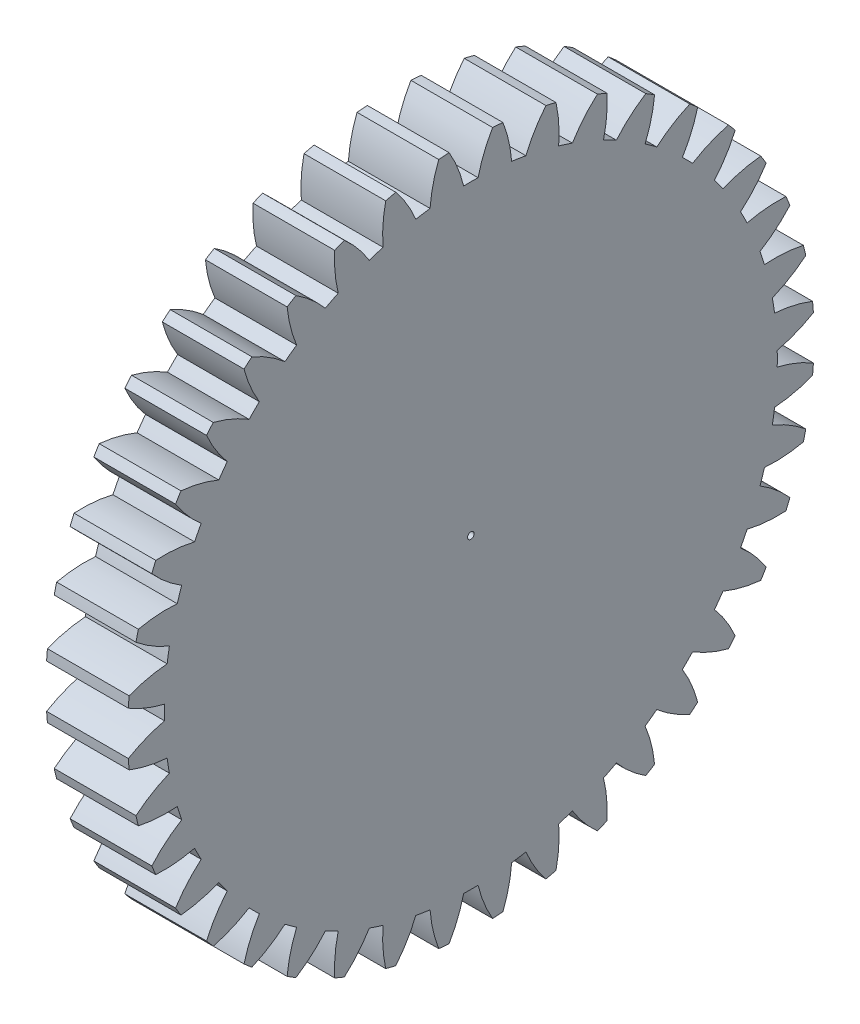
SolidWorks part; units mm, degrees
ref_plane "Plane1" through (0, 0, 0) normal (0, 0, 1) x (1, 0, 0)
ref_plane "Plane2" through (0, 0, 0) normal (0, 1, 0) x (1, 0, 0)
ref_plane "Plane3" through (0, 0, 0) normal (1, 0, 0) x (0, 0, -1)
sketch "HoldingSke" plane through (0, 0, 0) normal (0, 1, 0) x (1, 0, 0)
  line L0 (0, 0) -> (0.383, -0.3214)
  line L1 (-15, 0) -> (100, 0) construction
  line L2 (0, 0) -> (-2.1039, 2.3779)
  line L3 (0, 0) -> (-11.863, 4.5341)
  line L4 (0, 0) -> (6.6156, 5.5511)
  line L5 (0, 0) -> (-46.8476, -17.4728)
  line L6 (0, 0) -> (-8.2896, -5.593)
  line L7 (-2.1039, 2.3779) -> (8.6586, 51.2059)
  line L8 (-76.2, 54.61) -> (-76.1, 54.61)
  line L9 (-71.009, 38.7566) -> (-53.1078, 45.2721)
  line L10 (-76.2, 71.12) -> (104.1128, 71.12)
  line L11 (0, 0) -> (-10, 0)
  line L12 (-76.2, 101.6) -> (-76.133, 101.6)
  line L13 (24.9733, 27.94) -> (52.9518, 28.4284)
  line L14 (24.9733, 27.94) -> (24.9743, 27.94)
  line L15 (24.9733, 27.94) -> (100.4006, 29.5858)
  line L16 (-63.627, -2) -> (-12.827, -2)
  circle A0 centre (0, 0) radius 0.4
  circle A1 centre (0, 0) radius 37.499
  circle A2 centre (0, 0) radius 37.5
  circle A3 centre (0, 0) radius 0.4
  dimension "MHD" = 74.998
  dimension "Hub_dia" = 75
  dimension "Bore" = 0.8
  dimension "MBD" = 0.8
  dimension "Num_teeth" = 40
  dimension "Pitch_radius" = 180.3128
  dimension "Pitch" = 0.5
  dimension "Width" = 10
  dimension "Overall_len" = 50
  dimension "Show_teeth" = 40
  dimension "Thickness" = 10
  dimension "OAL" = 50.0001
  dimension "T_dim" = 0.1
  dimension "Ap" = 20
  dimension "H" = 19.05
  dimension "Backlash" = 0.067
  dimension "Addendum_fac" = 1
  dimension "Dedendum_fac" = 1.25
  dimension "Clearance_fac" = 0.25
  dimension "Dedendum_add" = 0.001
  dimension "Module" = 2
sketch "BasProSke" plane through (0, 0, 0) normal (0, 1, 0) x (1, 0, 0)
  line L0 (-10, 0) -> (60, 0) construction
  line L1 (0, 0) -> (0, 42)
  line L2 (0, 0) -> (10, 0)
  line L3 (10, 0) -> (10, 42)
  line L4 (10, 42) -> (0, 42)
  dimension "Diameter" = 84
  dimension "Thickness" = 10
revolve "Base-Revolve" add sketch "BasProSke" angle 360 about L0
sketch "TooCutSke" plane through (0, 0, 0) normal (1, 0, 0) x (0, 0, -1)
  line L1 (0, 0) -> (0, 107) construction
  line L2 (0, 0) -> (-1.6876, 39.9644) construction
  line L3 (0, 0) -> (-6.2726, 79.7007) construction
  line L4 (-1.6876, 39.9644) -> (-3.1363, 39.8504) construction
  arc A0 (0.8828, 37.4886) -> (-0.8828, 37.4886) centre (0, 0) ccw
  arc A1 (2.6784, 41.94) -> (-2.6784, 41.94) centre (0, 0) ccw
  circle A2 centre (0, 0) radius 40 construction
  circle A3 centre (0, 0) radius 37.5877 construction
  arc A4 (-0.8828, 37.4886) -> (-2.6784, 41.94) centre (-16.451, 33.7965) ccw
  arc A5 (2.6784, 41.94) -> (0.8828, 37.4886) centre (16.451, 33.7965) ccw
  dimension "Root_dia" = 74.998
  dimension "Overcut_dia" = 84.0508
  dimension "Pitch_dia" = 80
  dimension "Base_dia" = 75.1754
  dimension "Flank_rad" = 16
  dimension "Half_ang" = 4.5
  dimension "Half_CT" = 1.4531
extrude "ToothCut" cut sketch "TooCutSke" along normal through all
fillet "Breaks" [suppressed] radius 0.04 tangent propagation no
fillet "RootFillets" [suppressed] radius 0.501
pattern_circular "TeethCuts" count 40 every 9 about axis through (-10, 0, 0) along (1, 0, 0) of "ToothCut", "RootFillets", "Breaks"
sketch "HubNeaOneSke" plane through (0, 0, 0) normal (-1, 0, 0) x (0, 0, 1)
  circle A0 centre (0, 0) radius 37.499
  dimension "Diameter" = 74.998
extrude "HubNearOne" [suppressed] add sketch "HubNeaOneSke" along normal blind 40.0001
sketch "HubNeaBotSke" plane through (0, 0, 0) normal (-1, 0, 0) x (0, 0, 1)
  circle A0 centre (0, 0) radius 37.499
  dimension "Diameter" = 74.998
extrude "HubNearBoth" [suppressed] add sketch "HubNeaBotSke" along normal blind 20
ref_plane "FarPln" through (10, 0, 0) normal (1, 0, 0) x (0, 0, -1)
sketch "HubFarSke" plane through (10, 0, 0) normal (1, 0, 0) x (0, 0, -1)
  circle A0 centre (0, 0) radius 37.499
  dimension "Diameter" = 74.998
extrude "HubFar" [suppressed] add sketch "HubFarSke" along normal blind 20
sketch "BorSke" plane through (0, 0, 0) normal (1, 0, 0) x (0, 0, -1)
  circle A0 centre (0, 0) radius 0.4
  dimension "Diameter" = 0.8
extrude "Bore" cut sketch "BorSke" along normal mid plane 100.0001
sketch "KeySke" plane through (0, 0, 0) normal (1, 0, 0) x (0, 0, -1)
  line L0 (-0.05, 0) -> (-0.05, 0.5)
  line L1 (-0.05, 0.5) -> (0.05, 0.5)
  line L2 (0.05, 0.5) -> (0.05, 0)
  line L3 (0, 0) -> (0, 34) construction
  line L4 (-0.05, 0) -> (0.05, 0)
  dimension "Offset" = 0.5
  dimension "Width" = 0.1
extrude "Keyway" [suppressed] cut sketch "KeySke" along normal mid plane 100.0001
pattern_circular "Keyway2" [suppressed] count 2 every 90 about axis through (-10, 0, 0) along (1, 0, 0)
equation "' \"Module@HoldingSke\" = 6.35"
equation "' \"Num_teeth@HoldingSke\" = 12"
equation "' \"Ap@HoldingSke\" =  20"
equation "' \"Width@HoldingSke\" = 0.5 * 25.4"
equation "' \"Hub_dia@HoldingSke\"= 1 * 25.4"
equation "' \"Overall_len@HoldingSke\" = 1.0 * 25.4"
equation "' \"Bore@HoldingSke\" = 0.75 * 25.4"
equation "' \"T_dim@HoldingSke\" = 0.1 * 25.4"
equation "' \"Width@KeySke\" = 0.25 * 25.4"
equation "' \"Show_teeth@HoldingSke\" = 13"
equation "' \"Backlash@HoldingSke\" = 0.009 * 25.4"
equation "' \"Addendum_fac@HoldingSke\" = 1.0"
equation "' \"Dedendum_fac@HoldingSke\" = 1.25"
equation "' \"Dedendum_add@HoldingSke\" = 0.00005 * 25.4"
equation "' \"Clearance_fac@HoldingSke\" = 0.25"
equation "\"Pitch@HoldingSke\" = 1 / \"Module@HoldingSke\""
equation "\"Overcut_dia@TooCutSke\" = (\"Num_teeth@HoldingSke\" + 2 * \"Addendum_fac@HoldingSke\") / \"Pitch@HoldingSke\" + 0.002 * 25.4"
equation "\"Pitch_dia@TooCutSke\" = \"Num_teeth@HoldingSke\" / \"Pitch@HoldingSke\""
equation "\"Base_dia@TooCutSke\" = \"Num_teeth@HoldingSke\" / \"Pitch@HoldingSke\" * cos((\"Ap@HoldingSke\"  * 3.14159265 / 180))"
equation "\"Root_dia@TooCutSke\" = (\"Num_teeth@HoldingSke\" + 2) / \"Pitch@HoldingSke\" - 2 * (\"Addendum_fac@HoldingSke\" + \"Dedendum_fac@HoldingSke\") / \"Pitch@HoldingSke\" - \"Dedendum_add@HoldingSke\" * 2"
equation "\"Half_ang@TooCutSke\" = 180 / \"Num_teeth@HoldingSke\""
equation "\"Half_CT@TooCutSke\" = \"Num_teeth@HoldingSke\" / \"Pitch@HoldingSke\" * sin((3.14159265 / 2 / \"Num_teeth@HoldingSke\")) / 2 - 7 * \"Backlash@HoldingSke\" / 4"
equation "\"Flank_rad@TooCutSke\" = \"Num_teeth@HoldingSke\" / \"Pitch@HoldingSke\" / 5"
equation "\"Radius@RootFillets\" = \"Clearance_fac@HoldingSke\" / \"Pitch@HoldingSke\" + \"Dedendum_add@HoldingSke\""
equation "\"Break_rad@Breaks\" = 0.02 / \"Pitch@HoldingSke\""
equation "\"Thickness@HoldingSke\" = \"Width@HoldingSke\""
equation "\"OAL@HoldingSke\" = \"Thickness@HoldingSke\""
equation "\"MHD@HoldingSke\" = (\"Num_teeth@HoldingSke\" + 2) / \"Pitch@HoldingSke\" - 2 * (\"Addendum_fac@HoldingSke\" + \"Dedendum_fac@HoldingSke\")  / \"Pitch@HoldingSke\" - \"Dedendum_add@HoldingSke\" * 2"
equation "\"MBD@HoldingSke\" = (\"Num_teeth@HoldingSke\" + 2) / \"Pitch@HoldingSke\" - 2 * (\"Addendum_fac@HoldingSke\" + \"Dedendum_fac@HoldingSke\")  / \"Pitch@HoldingSke\" - \"Dedendum_add@HoldingSke\" * 2 - 0.002 * 25.4"
equation "\"MHD@HoldingSke\" = ((sgn( \"MHD@HoldingSke\" - \"Hub_dia@HoldingSke\" )-1)*( \"MHD@HoldingSke\" - \"Hub_dia@HoldingSke\" ))/-2+ \"Hub_dia@HoldingSke\""
equation "\"MBD@HoldingSke\" = ((sgn( \"MBD@HoldingSke\" - \"Bore@HoldingSke\" )-1)*( \"MBD@HoldingSke\" - \"Bore@HoldingSke\" ))/-2+ \"Bore@HoldingSke\""
equation "\"OAL@HoldingSke\" = ((sgn( \"OAL@HoldingSke\" - \"Overall_len@HoldingSke\" )+1)*( \"OAL@HoldingSke\" - \"Overall_len@HoldingSke\" ))/2 + \"Overall_len@HoldingSke\" + 0.000002 * 25.4"
equation "\"Num_teeth@TeethCuts\" = int( \"Show_teeth@HoldingSke\" ) + 1"
equation "\"Num_teeth@TeethCuts\" = ((sgn( \"Num_teeth@TeethCuts\" - \"Num_teeth@HoldingSke\" )-1)*( \"Num_teeth@TeethCuts\" - \"Num_teeth@HoldingSke\" ))/-2+ \"Num_teeth@HoldingSke\""
equation "\"Num_teeth@TeethCuts\" = ((sgn( \"Num_teeth@TeethCuts\" - 2.0)+1)*( \"Num_teeth@TeethCuts\" - 2.0))/2 +2.0"
equation "\"Angle@TeethCuts\" = 360.0 / \"Num_teeth@HoldingSke\""
equation "\"Diameter@BasProSke\" = (\"Num_teeth@HoldingSke\" + 2 * \"Addendum_fac@HoldingSke\") / \"Pitch@HoldingSke\""
equation "\"Thickness@BasProSke\"  = \"Thickness@HoldingSke\""
equation "' \"Fillet_rad@BasProSke\" =  \"Thickness@HoldingSke\" * 0.05"
equation "\"MHD@HoldingSke\" = ((sgn( \"MHD@HoldingSke\" - \"Root_dia@TooCutSke\" )-1)*( \"MHD@HoldingSke\" - \"Root_dia@TooCutSke\" ))/-2+ \"Root_dia@TooCutSke\""
equation "\"Diameter@HubNeaOneSke\" = \"MHD@HoldingSke\""
equation "\"Length@HubNearOne\" = \"OAL@HoldingSke\" - \"Thickness@BasProSke\""
equation "\"Diameter@HubNeaBotSke\" = \"MHD@HoldingSke\""
equation "\"Length@HubNearBoth\" = ( \"OAL@HoldingSke\" - \"Thickness@BasProSke\" ) / 2.0"
equation "\"Thickness@FarPln\" = \"Thickness@BasProSke\""
equation "\"Diameter@HubFarSke\" = \"MHD@HoldingSke\""
equation "\"Length@HubFar\" = ( \"OAL@HoldingSke\" - \"Thickness@BasProSke\" ) / 2.0"
equation "\"Diameter@BorSke\" = \"MBD@HoldingSke\""
equation "\"D1@Bore\" = \"OAL@HoldingSke\" * 2.0"
equation "\"D1@Keyway\" = \"OAL@HoldingSke\" * 2.0"
equation "\"Offset@KeySke\" = \"T_dim@HoldingSke\" + \"MBD@HoldingSke\" / 2.0"
